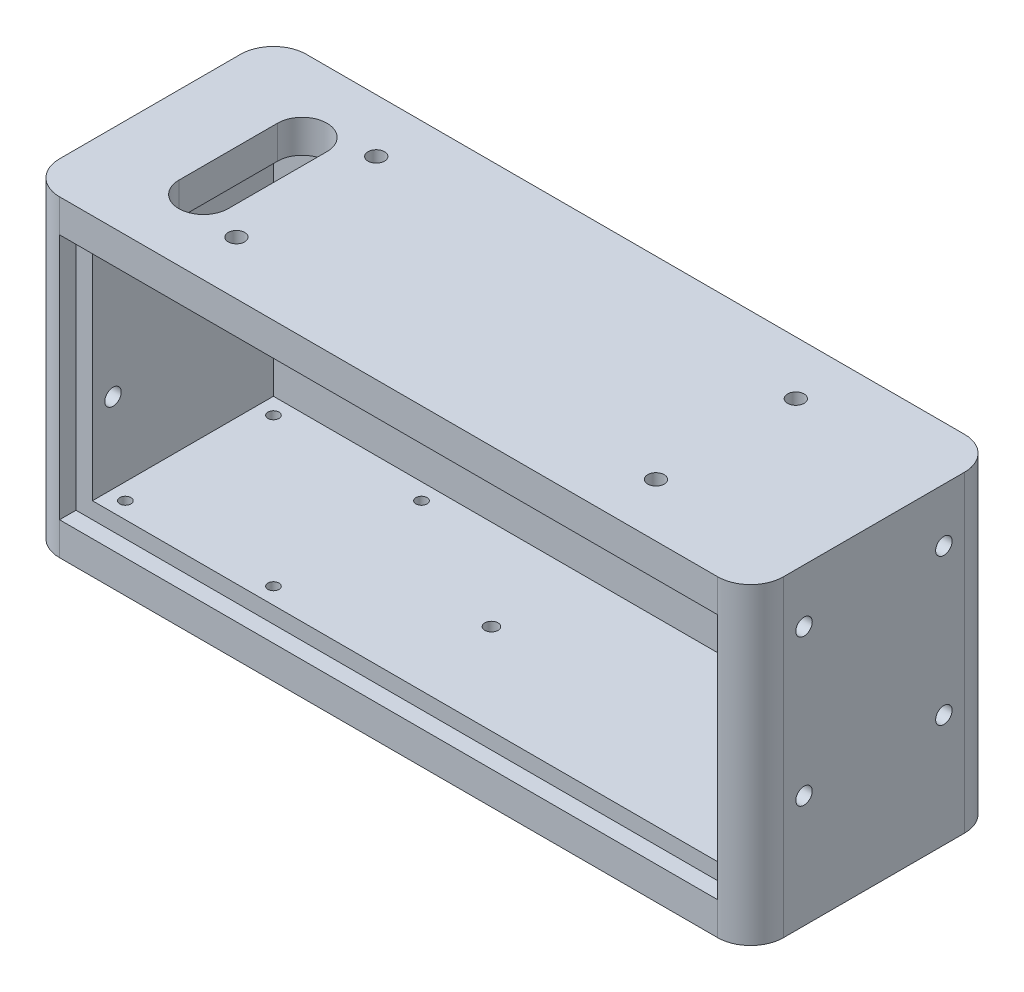
SolidWorks part; units mm, degrees
ref_plane "前视基准面" through (0, 0, 0) normal (0, 0, 1) x (1, 0, 0)
ref_plane "上视基准面" through (0, 0, 0) normal (0, 1, 0) x (1, 0, 0)
ref_plane "右视基准面" through (0, 0, 0) normal (1, 0, 0) x (0, 0, -1)
other "Configuration Table"
sketch "草图1" plane through (0, 0, 0) normal (0, 1, 0) x (1, 0, 0)
  line L1 (88, -30) -> (-88, -30)
  line L2 (88, -30) -> (88, 30)
  line L3 (88, 30) -> (-88, 30)
  line L4 (-88, -30) -> (-88, 30)
  line L5 (88, -30) -> (-88, 30) construction
  line L6 (88, 30) -> (-88, -30) construction
  point P0 (0, 0)
  dimension "D1" = 60
  dimension "D2" = 176
extrude "凸台-拉伸1" add sketch "草图1" along normal blind 76
sketch "草图3" plane through (0, 0, 30) normal (0, 0, 1) x (1, 0, 0)
  line L0 (-88, 0) -> (88, 0) construction
  line L1 (80, 8) -> (-80, 8)
  line L2 (80, 8) -> (80, 68)
  line L3 (80, 68) -> (-80, 68)
  line L4 (-80, 8) -> (-80, 68)
  line L5 (80, 8) -> (-80, 68) construction
  line L6 (80, 68) -> (-80, 8) construction
  line L7 (-88, 76) -> (-88, 0) construction
  line L8 (88, 76) -> (88, 0) construction
  line L9 (-88, 76) -> (88, 76) construction
  point P0 (0, 38)
  dimension "D1" = 8
  dimension "D2" = 8
  dimension "D3" = 8
  dimension "D4" = 8
extrude "切除-拉伸1" cut sketch "草图3" against normal blind 52
fillet "圆角1" radius 8 4 edges at (-88, 38, -30) (88, 38, -30) (88, 38, 30) (-88, 38, 30)
sketch "草图4" plane through (-88, 0, 0) normal (-1, 0, 0) x (0, 0, 1)
  line L5 (-22, 76) -> (22, 76) construction
  line L9 (17, 27.4) -> (-17, 27.4) construction
  line L10 (17, 27.4) -> (17, 63) construction
  line L11 (17, 63) -> (-17, 63) construction
  line L13 (-17, 27.4) -> (-17, 63) construction
  line L14 (17, 27.4) -> (-17, 63) construction
  line L15 (17, 63) -> (-17, 27.4) construction
  line L18 (30, 68) -> (30, 8) construction
  line L19 (-30, 0) -> (-30, 76) construction
  line L22 (-17, 45.2) -> (17, 45.2) construction
  line L23 (0, 63) -> (0, 27.4) construction
  circle A8 centre (-17, 63) radius 2
  circle A9 centre (17, 63) radius 2
  circle A10 centre (17, 27.4) radius 2
  circle A11 centre (-17, 27.4) radius 2
  point P0 (0, 45.2)
  dimension "D5" = 4
  dimension "D1" = 13
  dimension "D2" = 13
  dimension "D3" = 13
  dimension "D4" = 35.6
extrude "切除-拉伸2" cut sketch "草图4" against normal through all
sketch "草图5" plane through (0, 8, 0) normal (0, 1, 0) x (1, 0, 0)
  line L0 (-88, -30) -> (-88, 30) construction
  line L1 (-40, -18) -> (-76, -18) construction
  line L2 (-40, -18) -> (-40, 18) construction
  line L3 (-40, 18) -> (-76, 18) construction
  line L4 (-76, -18) -> (-76, 18) construction
  line L5 (-40, -18) -> (-76, 18) construction
  line L6 (-40, 18) -> (-76, -18) construction
  line L8 (-76, 0) -> (-40, 0) construction
  line L9 (-58, -18) -> (-58, 18) construction
  circle A0 centre (-76, 18) radius 1.35
  circle A1 centre (-40, 18) radius 1.35
  circle A2 centre (-40, -18) radius 1.35
  circle A3 centre (-76, -18) radius 1.35
  point P0 (-58, 0)
  dimension "D4" = 2.7
  dimension "D1" = 12
  dimension "D2" = 36
  dimension "D3" = 36
extrude "切除-拉伸3" cut sketch "草图5" against normal through all
sketch "草图6" plane through (0, 76, 0) normal (0, 1, 0) x (1, 0, 0)
  line L0 (88, -22) -> (88, 22) construction
  line L1 (52, -17) -> (-50, -17) construction
  line L2 (52, -17) -> (52, 17) construction
  line L3 (52, 17) -> (-50, 17) construction
  line L4 (-50, -17) -> (-50, 17) construction
  line L5 (52, -17) -> (-50, 17) construction
  line L6 (52, 17) -> (-50, -17) construction
  line L7 (-80, -30) -> (80, -30) construction
  line L8 (1, 17) -> (1, -17) construction
  line L9 (-50, 0) -> (52, 0) construction
  line L10 (80, 30) -> (-80, 30) construction
  line L11 (-63, -12) -> (-63, 12) construction
  line L12 (-69, -12) -> (-69, 12)
  line L13 (-57, -12) -> (-57, 12)
  circle A0 centre (-50, 17) radius 2
  circle A1 centre (52, 17) radius 2
  circle A2 centre (52, -17) radius 2
  circle A3 centre (-50, -17) radius 2
  arc A4 (-69, -12) -> (-57, -12) centre (-63, -12) ccw
  arc A5 (-57, 12) -> (-69, 12) centre (-63, 12) ccw
  point P0 (1, 0)
  point P20 (-63, 0)
  point P29 (-63, 18)
  point P30 (-63, -18)
  dimension "D4" = 4
  dimension "D1" = 36
  dimension "D2" = 34
  dimension "D3" = 102
  dimension "D5" = 13
  dimension "D6" = 12
  dimension "D7" = 12
  dimension "D8" = 12
extrude "切除-拉伸4" cut sketch "草图6" against normal up to surface (8 mm away) up to face at (0, 68, 4)
sketch "草图7" plane through (0, 8, 0) normal (0, 1, 0) x (1, 0, 0)
  line L0 (70, 16.5) -> (70, -16.5) construction
  line L2 (88, -22) -> (88, 22) construction
  circle A0 centre (70, 16.5) radius 1.6
  circle A1 centre (70, -16.5) radius 1.6
  circle A2 centre (-5, 0) radius 1.6
  point P6 (70, 0)
  dimension "D1" = 3.2
  dimension "D2" = 3.2
  dimension "D3" = 3.2
  dimension "D4" = 33
  dimension "D5" = 75
  dimension "D6" = 18
extrude "切除-拉伸5" cut sketch "草图7" against normal through all
sketch "草图8" plane through (0, 0, 0) normal (0, -1, 0) x (1, 0, 0)
  line L0 (-58, 18) -> (-58, -18) construction
  line L3 (-76, 0) -> (-40, 0) construction
  circle A0 centre (-76, 18) radius 2.5
  circle A1 centre (-40, 18) radius 2.5
  circle A2 centre (-40, -18) radius 2.5
  circle A3 centre (-76, -18) radius 2.5
  circle A4 centre (-5, 0) radius 3
  circle A5 centre (70, 16.5) radius 3
  circle A6 centre (70, -16.5) radius 3
  dimension "D1" = 5
  dimension "D2" = 6
  dimension "D3" = 6
  dimension "D4" = 6
extrude "切除-拉伸6" cut sketch "草图8" against normal blind 4
sketch "草图9" plane through (-88, 0, 0) normal (-1, 0, 0) x (0, 0, 1)
  line L0 (30, 76) -> (22, 76) construction
  line L1 (22, 72) -> (26, 72)
  line L2 (22, 72) -> (22, 4)
  line L3 (22, 4) -> (26, 4)
  line L4 (26, 72) -> (26, 4)
  line L5 (22, 0) -> (30, 0) construction
  line L6 (30, 68) -> (30, 8) construction
  dimension "D1" = 4
  dimension "D2" = 4
  dimension "D3" = 4
  dimension "D4" = 4
extrude "切除-拉伸7" cut sketch "草图9" against normal blind 172
sketch "草图10" plane through (0, 0, -30) normal (0, 0, -1) x (-1, 0, 0)
  line L0 (-80, 27) -> (80, 27) construction
  line L1 (-80, 76) -> (-80, 0) construction
  line L2 (80, 0) -> (80, 76) construction
  line L3 (-80, 0) -> (80, 0) construction
  text T0 "XUANWU" font "Georgia" height 22
  dimension "D1" = 27
extrude "切除-拉伸8" cut sketch "草图10" against normal blind 2
